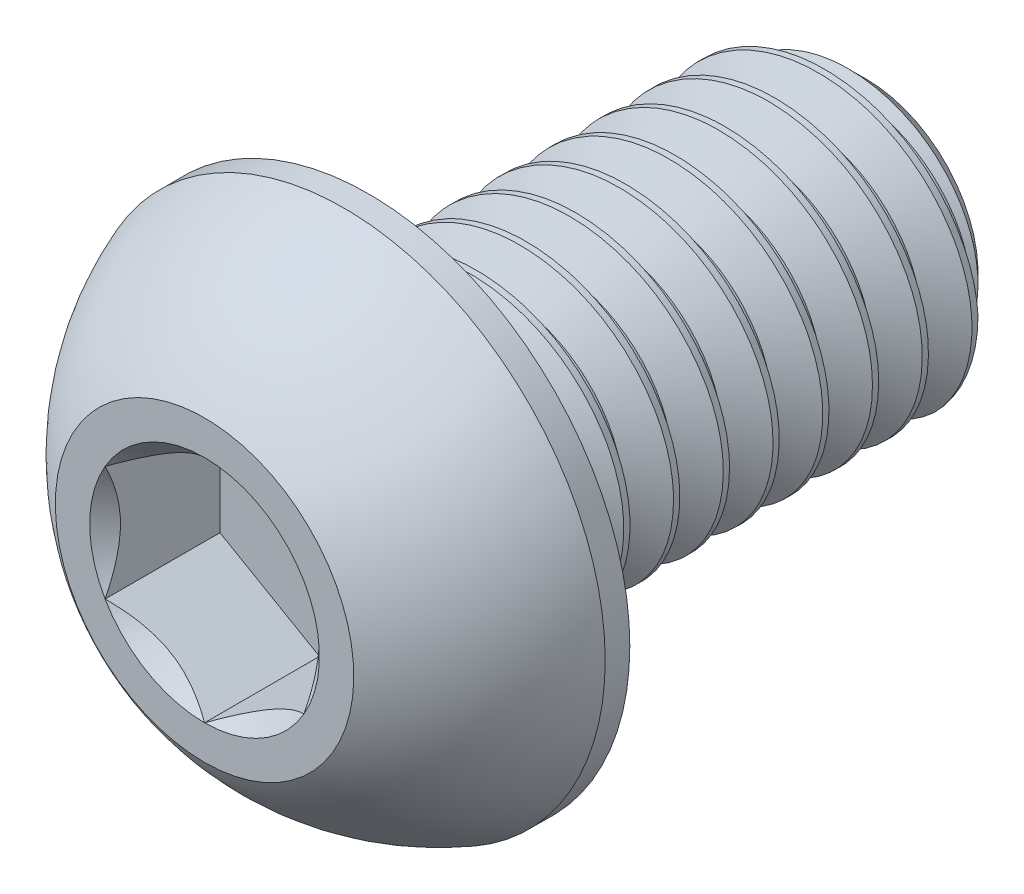
SolidWorks part; units mm, degrees
ref_plane "Front" through (0, 0, 0) normal (0, 0, 1) x (1, 0, 0)
ref_plane "Top" through (0, 0, 0) normal (0, 1, 0) x (1, 0, 0)
ref_plane "Right" through (0, 0, 0) normal (1, 0, 0) x (0, 0, -1)
sketch "Sketch1" plane through (0, 0, 0) normal (1, 0, 0) x (0, 0, -1)
  line L2 (3.3, 3) -> (13.3, 3)
  line L3 (13.3, 3) -> (13.3, 0)
  line L4 (13.3, 0) -> (3.3, 0)
  line L6 (2.805, 5.25) -> (3.3, 5.25) construction
  line L7 (13.3, 3) -> (13.3, -3) construction
  line L8 (0, 0) -> (3.3, 0) construction
  line L9 (3.3, 5.25) -> (3.3, -5.25) construction
  line L11 (3.3, 3) -> (3.3, 0)
  line L13 (0, 2) -> (0, -2) construction
  line L14 (0, 2) -> (0, 3) construction
  line L15 (13.3, -3) -> (12.3, -3) construction
  arc A3 (0, 3) -> (2.805, 5.25) centre (4.7113, 0) cw construction
  dimension "D1" = 0.495
  dimension "Pitch" = 1
revolve "Revolve1" add sketch "Sketch1" angle 360 mid plane about L4
sketch "Sketch7" plane through (0, 0, 0) normal (1, 0, 0) x (0, 0, -1)
  line L6 (2.805, 5.25) -> (3.3, 5.25) construction
  line L8 (0, 0) -> (3.3, 0) construction
  line L11 (3.3, 5.25) -> (3.3, -5.25) construction
  line L12 (2.805, 5.25) -> (3.3, 5.25)
  line L13 (0, 0) -> (3.3, 0)
  line L14 (0, 2) -> (0, -2) construction
  line L15 (3.3, 5.25) -> (3.3, 0)
  line L16 (0, 3) -> (0, 0)
  arc A2 (2.805, 5.25) -> (0, 3) centre (4.7113, 0) ccw construction
  arc A3 (2.805, 5.25) -> (0, 3) centre (4.7113, 0) ccw
revolve "Revolve2" add sketch "Sketch7" angle 360 mid plane about L13
sketch "Sketch5" plane through (0, 0, 0) normal (0, 0, 1) x (1, 0, 0)
  line L1 (2, -1.1547) -> (2, 1.1547)
  line L2 (2, 1.1547) -> (0, 2.3094)
  line L3 (0, 2.3094) -> (-2, 1.1547)
  line L4 (-2, 1.1547) -> (-2, -1.1547)
  line L5 (-2, -1.1547) -> (0, -2.3094)
  line L6 (0, -2.3094) -> (2, -1.1547)
  circle A0 centre (0, 0) radius 2 construction
extrude "Cut-Extrude2" cut sketch "Sketch5" against normal blind 2.31
sketch "Sketch6" plane through (0, 0, 0) normal (0, 0, 1) x (1, 0, 0)
  circle A0 centre (0, 0) radius 2.3094
extrude "Cut-Extrude3" cut sketch "Sketch6" against normal blind 2.31 draft 45
sketch "Sketch11" plane through (0, 0, 0) normal (1, 0, 0) x (0, 0, -1)
  line L0 (3.3, -5.25) -> (3.3, 5.25)
  point P4 (3.3, 0)
split "Split1" trim tools "Sketch11" bodies to split 113 resulting bodies 119 120
sketch "Sketch10" plane through (0, 0, 0) normal (1, 0, 0) x (0, 0, -1)
  line L0 (13.3, 3) -> (13.3, -3) construction
  point P0 (11.8, -3)
  dimension "D1" = 1.5
sketch "Sketch3" plane through (0, 0, -13.3) normal (0, 0, -1) x (-1, 0, 0)
  circle A0 centre (0, 0) radius 3
curve "Helix/Spiral1" pitch 1 height 11 turns 11
sketch "Sketch2" plane through (0, 0, 0) normal (1, 0, 0) x (0, 0, -1)
  line L0 (13.2375, 3.1083) -> (14.2375, 3.1083) construction
  line L1 (14.2375, 3.1083) -> (13.7375, 2.2422) construction
  line L2 (13.7375, 2.2422) -> (13.2375, 3.1083) construction
  line L3 (13.7375, 3.1083) -> (13.7375, 3) construction
  line L4 (13.7375, 3) -> (13.7375, 2.3505) construction
  line L5 (13.7375, 2.3505) -> (13.7375, 2.2422) construction
  line L6 (13.675, 2.3505) -> (13.8, 2.3505)
  line L7 (13.3, 3) -> (14.175, 3) construction
  line L8 (13.2687, 3.0541) -> (14.2062, 3.0541)
  line L9 (13.2687, 3.0541) -> (13.675, 2.3505)
  line L10 (14.2062, 3.0541) -> (13.8, 2.3505)
  point P10 (13.7375, 2.3505)
  point P13 (13.7375, 3)
  point P16 (13.7375, 3.0541)
  dimension "D1" = 1
  dimension "D2" = 0.125
chamfer "Chamfer1" distance 0.75 angle 45 1 edges at (0, 3, -13.3)
sweep "Cut-Sweep1" cut profiles "Sketch2" path "Helix/Spiral1" align with end faces yes
combine bodies "Combine1" operation type add bodies to combine 120 114
equation "\"D3@Helix/Spiral1\" = \"Lg@Sketch1\" + \"D4@Helix/Spiral1\""
equation "\"D1@Chamfer1\" = \"D4@Helix/Spiral1\" * .75"
equation "\"D1@Cut-Extrude2\" = \"Head Ht@Sketch1\" * .7"
equation "\"D1@Sketch1\" = \"Head Ht@Sketch1\" * .15"
equation "\"D1@Sketch10\" = \"D4@Helix/Spiral1\" * 1.5"
equation "\"D1@Cut-Extrude3\" = \"D1@Cut-Extrude2\""
equation "\"D4@Helix/Spiral1\"=\"Pitch@Sketch1\""
equation "\"D1@Sketch2\"=\"Pitch@Sketch1\""
equation "\"D2@Sketch2\"=\"D1@Sketch2\"/8"
